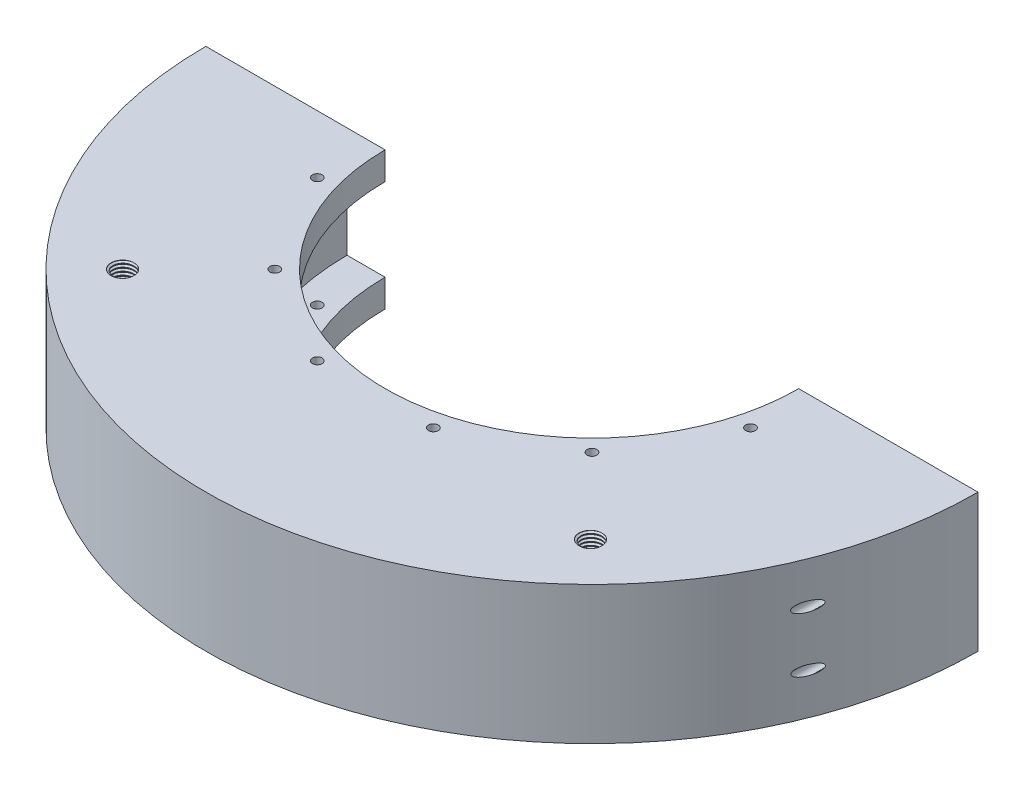
SolidWorks part; units mm, degrees
material "6061-T6 (SS)"
ref_plane "Front Plane" through (0, 0, 0) normal (0, 0, 1) x (1, 0, 0)
ref_plane "Top Plane" through (0, 0, 0) normal (0, 1, 0) x (1, 0, 0)
ref_plane "Right Plane" through (0, 0, 0) normal (1, 0, 0) x (0, 0, -1)
sketch "Sketch1" plane through (0, 0, 0) normal (0, 0, 1) x (1, 0, 0)
  line L0 (0, 0) -> (56.388, 0) construction
  line L1 (56.388, 0) -> (56.388, 9.525)
  line L2 (56.388, 0) -> (56.388, -9.525)
  line L3 (56.388, 9.525) -> (47.625, 9.525)
  line L4 (56.388, -9.525) -> (47.625, -9.525)
  line L5 (47.625, 9.525) -> (47.625, 15.875)
  line L6 (47.625, 15.875) -> (88.9, 15.875)
  line L7 (47.625, -9.525) -> (47.625, -15.875)
  line L8 (47.625, -15.875) -> (88.9, -15.875)
  line L9 (88.9, 15.875) -> (88.9, -15.875)
  line L10 (0, 22.5393) -> (0, -21.157) construction
  dimension "D1" = 56.388
  dimension "D2" = 9.525
  dimension "D3" = 9.525
  dimension "D4" = 47.625
  dimension "D5" = 6.35
  dimension "D6" = 6.35
  dimension "D7" = 88.9
  dimension "D8" = 47.625
revolve "Revolve1" add sketch "Sketch1" angle 180 about L10
sketch "Sketch2" plane through (0, 15.875, 0) normal (0, 1, 0) x (1, 0, 0)
  line L0 (49.8787, -13.3649) -> (0, 0) construction
  line L1 (0, 0) -> (55.1424, 0) construction
  line L2 (88.9, 0) -> (47.625, 0) construction
  point P4 (49.8787, -13.3649)
  dimension "D1" = 15
  dimension "D2" = 51.6382
hole_wizard "Tap Drill for #4-40 Tap1" positions "3DSketch1" profile "Sketch3" hole size "#4-40" standard "ANSI Inch" end condition through all
sketch3d "3DSketch1"
  point P0 (49.8787, 15.875, 13.3649)
sketch "Sketch3" plane through (49.8787, 15.875, 13.3649) normal (1, 0, 0) x (0, 0, 1)
  line L0 (0, 0) -> (0, 31.75)
  line L1 (0, 31.75) -> (1.1303, 31.75)
  line L2 (1.1303, 31.75) -> (1.1303, 0)
  line L5 (1.1303, 0) -> (0, 0)
  line L11 (0, -6.35) -> (0, 107.95) construction
  dimension "Thru Hole Dia." = 2.2606
  dimension "Thru Hole Depth" = 31.75
pattern_circular "CirPattern1" count 12 over 360 about axis through (0, 15.875, 0) along (0, 1, 0) skipping 1, 2, 3, 4, 5, 6 of "Tap Drill for #4-40 Tap1"
sketch "Sketch4" plane through (0, 0, 0) normal (0, 0, -1) x (-1, 0, 0)
  line L2 (47.625, -15.875) -> (88.9, -15.875) construction
  line L3 (88.9, -15.875) -> (88.9, 15.875) construction
  circle A0 centre (82.55, 6.35) radius 1.1303
  circle A1 centre (82.55, -6.35) radius 1.1303
  dimension "D1" = 2.2606
  dimension "D2" = 2.2606
  dimension "D3" = 12.7
  dimension "D4" = 6.35
  dimension "D5" = 9.525
  dimension "D6" = 6.35
extrude "Cut-Extrude1" cut sketch "Sketch4" against normal up to next
sketch "Sketch6" plane through (0, 0, 0) normal (0, 0, -1) x (-1, 0, 0)
  line L0 (-88.9, -15.875) -> (-88.9, 15.875) construction
  line L1 (-47.625, -15.875) -> (-88.9, -15.875) construction
  circle A0 centre (-82.55, 6.35) radius 1.1303
  circle A1 centre (-82.5792, -6.35) radius 1.1303
  dimension "D3" = 2.2606
  dimension "D4" = 2.2606
  dimension "D1" = 6.35
  dimension "D2" = 9.525
  dimension "D5" = 12.7
extrude "Cut-Extrude2" cut sketch "Sketch6" against normal up to next and the other way through all
sketch "Sketch7" plane through (0, 15.875, 0) normal (0, 1, 0) x (1, 0, 0)
  line L0 (88.9, 0) -> (47.625, 0) construction
  line L1 (-88.9, 0) -> (-47.625, 0) construction
  line L2 (0, 0) -> (0, -88.9) construction
  line L3 (0, 0) -> (-70.8597, -101.1982) construction
  line L4 (0, 0) -> (74.4736, -106.3593) construction
  line L5 (50.9909, -72.8226) -> (0, -63.5)
  line L6 (0, 0) -> (111.1038, 0) construction
  line L7 (53.8815, -53.8815) -> (0, 0) construction
  line L8 (0, 0) -> (-96.8039, 0) construction
  line L9 (0, 0) -> (-77.4, -77.4) construction
  line L10 (0, -63.5) -> (-50.9909, -72.8226)
  line L11 (72.8226, -50.9909) -> (63.5, 0)
  line L12 (0, 0) -> (127.391, -89.2001) construction
  line L13 (0, 0) -> (-97.05, -67.9551) construction
  line L14 (-72.8226, -50.9909) -> (-63.5, 0)
  arc A0 (63.5, 0) -> (-63.5, 0) centre (0, 0) cw
  circle A3 centre (53.8815, -53.8815) radius 6.35
  circle A4 centre (-53.8815, -53.8815) radius 6.35
  arc A5 (-88.9, 0) -> (88.9, 0) centre (0, 0) ccw construction
  arc A6 (50.9909, -72.8226) -> (-50.9909, -72.8226) centre (0, 0) cw
  dimension "D1" = 63.5
  dimension "D2" = 12.7
  dimension "D6" = 12.7
  dimension "D3" = 76.2
  dimension "D4" = 45
  dimension "D5" = 45
  dimension "D7" = 76.2
  dimension "D8" = 35
  dimension "D9" = 35
  dimension "D10" = 35
  dimension "D11" = 35
sketch "Sketch8" plane through (0, 15.875, 0) normal (0, 1, 0) x (1, 0, 0)
  line L0 (53.8815, -53.8815) -> (0, 0) construction
  line L1 (0, 0) -> (-53.8815, -53.8815) construction
  line L2 (0, 0) -> (0, -87.0628) construction
  line L3 (93.5942, 0) -> (-92.7386, 0) construction
  circle A0 centre (53.8815, -53.8815) radius 2.413
  circle A1 centre (-53.8815, -53.8815) radius 2.413
  dimension "D1" = 4.826
  dimension "D2" = 4.826
  dimension "D3" = 45
  dimension "D4" = 45
  dimension "D5" = 76.2
  dimension "D6" = 76.2
extrude "Cut-Extrude4" cut sketch "Sketch8" against normal blind 12.7
thread "Thread1" pitch 0.7937 start angle 0, offset 0, length 0, pitch 0.7937, diameter 4.826
ref_plane "Plane2" through (56.2945, 3.175, 53.8815) normal (0, 0, 1) x (1, 0, 0)
sketch "Thread Profile2" plane through (56.2945, 3.175, 53.8815) normal (0, 0, 1) x (1, 0, 0)
  line L0 (0, 0) -> (0, 0.7937) construction
  line L1 (0, 0) -> (0.4296, 0.248)
  line L2 (0.4296, 0.248) -> (0.4296, 0.3473)
  line L3 (0.4296, 0.3473) -> (0, 0.5953)
  line L4 (0.4296, 0.2977) -> (0, 0.2977) construction
  line L11 (0, 0) -> (0, 0.5953)
  point P2 (0, 0)
  dimension "Pitch" = 0.7937
  dimension "Profile_Angle" = 60
  dimension "Profile_Land" = 0.0992
  dimension "Profile_Height" = 0.4296
thread "Thread2" pitch 0.7937 profile "Thread Profile3" start angle 0, offset 0, length 0, pitch 0.7937, diameter 4.826
ref_plane "Plane3" through (-51.4685, 3.175, 53.8815) normal (0, 0, 1) x (1, 0, 0)
sketch "Thread Profile3" plane through (-51.4685, 3.175, 53.8815) normal (0, 0, 1) x (1, 0, 0)
  line L0 (0, 0) -> (0, 0.7937) construction
  line L1 (0, 0) -> (0.4296, 0.248)
  line L2 (0.4296, 0.248) -> (0.4296, 0.3473)
  line L3 (0.4296, 0.3473) -> (0, 0.5953)
  line L4 (0.4296, 0.2977) -> (0, 0.2977) construction
  line L11 (0, 0) -> (0, 0.5953)
  point P2 (0, 0)
  dimension "Pitch" = 0.7937
  dimension "Profile_Angle" = 60
  dimension "Profile_Land" = 0.0992
  dimension "Profile_Height" = 0.4296
